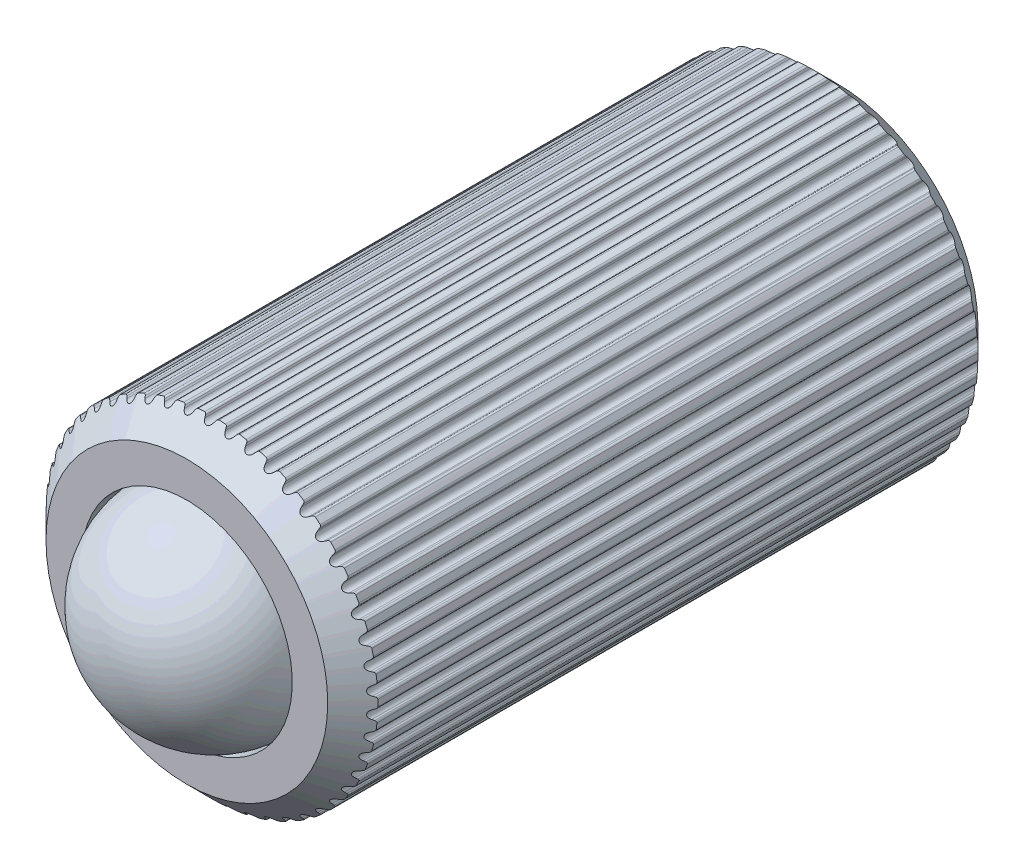
SolidWorks part; units mm, degrees
ref_plane "Front Plane" through (0, 0, 0) normal (0, 0, 1) x (1, 0, 0)
ref_plane "Top Plane" through (0, 0, 0) normal (0, 1, 0) x (1, 0, 0)
ref_plane "Right Plane" through (0, 0, 0) normal (1, 0, 0) x (0, 0, -1)
sketch "Sketch1" plane through (0, 0, 0) normal (1, 0, 0) x (0, 0, -1)
  line L0 (3.683, 0) -> (-3.683, 0) construction
  line L1 (-3.683, 0) -> (-4.572, 0) construction
  line L2 (0, -1.8796) -> (0, 1.8796) construction
  line L3 (-3.683, -1.1938) -> (-3.683, 1.1938) construction
  line L4 (-3.683, 1.1938) -> (-3.3782, 1.1938) construction
  line L5 (-3.683, 1.1938) -> (-3.683, 1.5955) construction
  line L6 (-3.683, 1.5955) -> (-3.3989, 1.8796) construction
  line L7 (-3.3989, 1.8796) -> (0, 1.8796) construction
  line L8 (-3.4616, 1.8169) -> (0, 1.8169) construction
  line L9 (3.683, 1.5955) -> (3.3989, 1.8796) construction
  line L10 (-4.572, 0) -> (-4.572, 1.1938) construction
  line L11 (3.683, 1.5955) -> (3.683, 0) construction
  line L12 (0, -1.8796) -> (3.3989, -1.8796) construction
  line L13 (0, 1.8796) -> (3.3989, 1.8796) construction
  circle A0 centre (-3.3782, 0) radius 1.1938 construction
  circle A1 centre (-2.4892, 0) radius 1.1938 construction
  point P4 (0, 0)
  point P9 (0, 0)
  point P12 (-3.683, 0)
  dimension "Body Length" = 7.366
  dimension "Extended Nose Length" = 0.889
  dimension "Body Diameter" = 3.7592
  dimension "Nose Diameter" = 2.3876
  dimension "D1" = 45
  dimension "Knurling Depth" = 0.0627
sketch "Sketch5" plane through (0, 0, 0) normal (0, 0, 1) x (1, 0, 0)
  line L0 (0, -1.1938) -> (0, 1.1938) construction
  line L1 (-0.0668, 1.8784) -> (-0.0313, 1.8169) construction
  line L2 (-0.0313, 1.8169) -> (0.0313, 1.8169) construction
  line L3 (0.0313, 1.8169) -> (0.0668, 1.8784) construction
  line L5 (0, 1.8169) -> (0, 1.8796) construction
  circle A0 centre (0, 0) radius 1.8796 construction
  point P0 (0, 1.8169)
  point P2 (0, 1.8796)
  dimension "D1" = 60
sketch "Sketch2" plane through (0, 0, 0) normal (1, 0, 0) x (0, 0, -1)
  line L2 (-3.683, 1.1938) -> (-3.683, 1.5955)
  line L3 (-3.3989, 1.8796) -> (3.3989, 1.8796)
  line L6 (-3.683, 1.1938) -> (-2.4892, 1.1938)
  line L7 (3.683, 1.5955) -> (3.683, 0)
  line L8 (3.683, 0) -> (-1.2954, 0)
  line L9 (-3.683, 1.5955) -> (-3.3989, 1.8796) construction
  line L10 (-3.683, 1.5955) -> (-3.3989, 1.8796)
  line L11 (3.683, 1.5955) -> (3.3989, 1.8796) construction
  line L12 (3.683, 1.5955) -> (3.3989, 1.8796)
  circle A0 centre (-2.4892, 0) radius 1.1938 construction
  arc A1 (-1.2954, 0) -> (-2.4892, 1.1938) centre (-2.4892, 0) ccw
revolve "Revolve1" add sketch "Sketch2" angle 360 about L0
sketch "Sketch3" plane through (0, 0, 0) normal (1, 0, 0) x (0, 0, -1)
  line L0 (3.683, 0) -> (-3.683, 0) construction
  line L1 (3.683, 0) -> (-3.683, 0) construction
  line L2 (-3.683, 0) -> (-4.572, 0) construction
  line L3 (-3.683, 0) -> (-4.572, 0) construction
  line L4 (-2.1844, 0) -> (-4.572, 0)
  circle A0 centre (-3.3782, 0) radius 1.1938 construction
  arc A1 (-2.1844, 0) -> (-4.572, 0) centre (-3.3782, 0) ccw
revolve "Revolve2" add sketch "Sketch3" angle 360 about L1
sketch "Sketch6" plane through (0, 0, 0) normal (0, 0, 1) x (1, 0, 0)
  line L0 (-0.0313, 1.8169) -> (0.0313, 1.8169) construction
  line L1 (0.0313, 1.8169) -> (0.0668, 1.8784) construction
  line L2 (-0.0668, 1.8784) -> (-0.0313, 1.8169) construction
  line L3 (-0.0313, 1.8169) -> (0.0313, 1.8169) construction
  line L4 (0.0313, 1.8169) -> (0.0668, 1.8784) construction
  line L5 (-0.0668, 1.8784) -> (-0.0313, 1.8169) construction
  line L6 (-0.0491, 1.8477) -> (-0.0668, 1.8784)
  line L7 (-0.0668, 1.8784) -> (-0.0941, 1.926)
  line L8 (-0.0941, 1.926) -> (0.0943, 1.926)
  line L9 (0.0491, 1.8477) -> (0.0943, 1.926)
  arc A0 (-0.0491, 1.8477) -> (0.0491, 1.8477) centre (0, 1.8715) ccw
extrude "Cut-Extrude1" cut sketch "Sketch6" against normal through all both and the other way through all
fillet "Fillet1" radius 0.0254 2 edges at (0.0668, 1.8784, 0) (-0.0668, 1.8784, 0)
pattern_circular "CirPattern1" count 50 over 360 about axis through (0, 0, -3.683) along (0, 0, 1) of "Cut-Extrude1", "Fillet1" reverse direction yes
equation "\"Knurling Depth@Sketch1\"=\"Body Diameter@Sketch1\" / 60"
